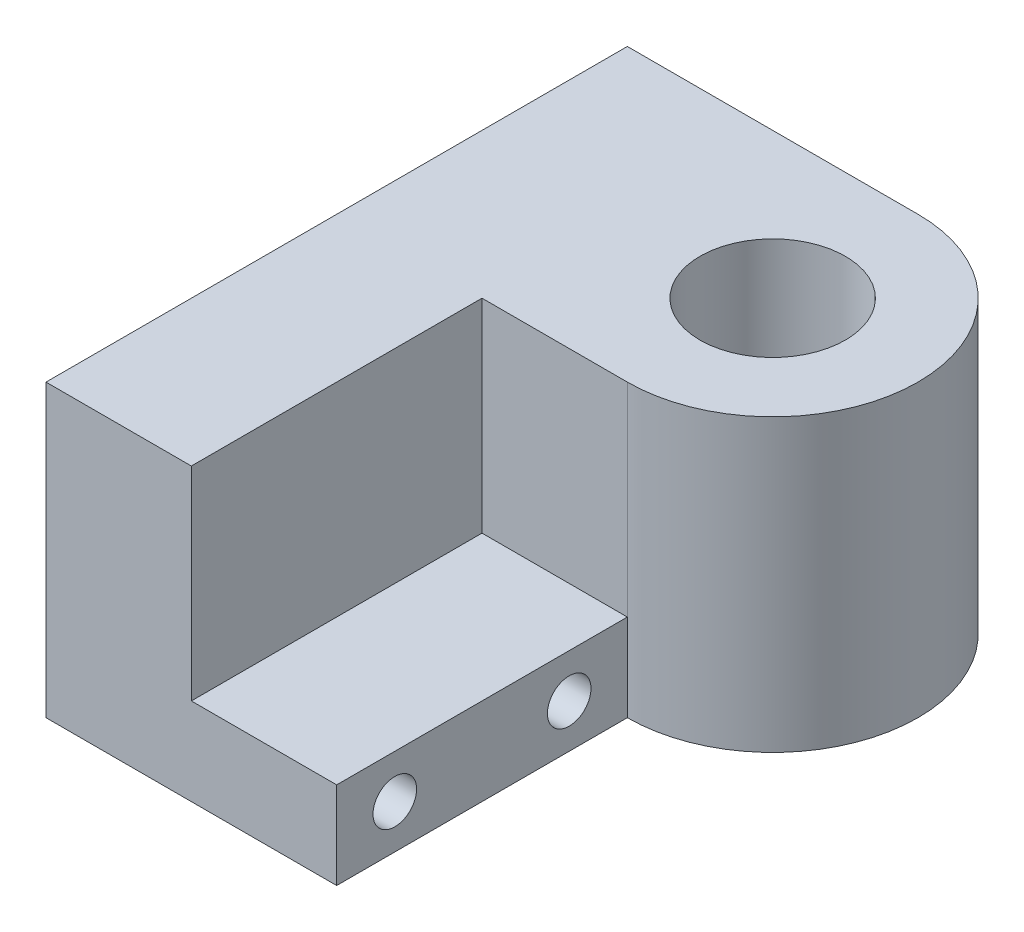
SolidWorks part; units mm, degrees
material "AISI 304"
ref_plane "Alzado" through (0, 0, 0) normal (0, 0, 1) x (1, 0, 0)
ref_plane "Planta" through (0, 0, 0) normal (0, 1, 0) x (1, 0, 0)
ref_plane "Vista lateral" through (0, 0, 0) normal (1, 0, 0) x (0, 0, -1)
sketch "Croquis3" plane through (0, 0, 0) normal (0, 1, 0) x (1, 0, 0)
  line L0 (0, 50) -> (-100, 50)
  line L1 (-100, 50) -> (-100, -150)
  line L2 (-100, -150) -> (-50, -150)
  line L3 (-50, -150) -> (-50, -50)
  line L4 (-50, -150) -> (0, -150)
  line L5 (0, -150) -> (0, -50)
  line L6 (0, -50) -> (-50, -50)
  circle A0 centre (0, 0) radius 25
  arc A1 (0, -50) -> (0, 50) centre (0, 0) ccw
  dimension "D1" = 100
  dimension "D3" = 200
  dimension "D4" = 100
  dimension "D2" = 50
  dimension "D5" = 100
extrude "Saliente-Extruir2" add sketch "Croquis3" along normal blind 100 contours L6 A1 L0 L1 L2 L3 A0 region at (-46.6688, 0, 29.4751)
extrude "Saliente-Extruir3" add sketch "Croquis3<3>" along normal blind 30 contours L5 L6 L3 L4 region at (-25, 0, 100)
sketch "Croquis3<3>" plane through (0, 0, 0) normal (0, 1, 0) x (1, 0, 0) same geometry as "Croquis3"
sketch "Croquis4" plane through (0, 0, 0) normal (1, 0, 0) x (0, 0, -1)
  line L0 (-150, 15) -> (-50, 15) construction
  line L1 (-150, 30) -> (-150, 0) construction
  line L2 (-50, 30) -> (-50, 0) construction
  line L3 (-100, 30) -> (-100, 0) construction
  line L4 (-150, 30) -> (-50, 30) construction
  line L5 (-150, 0) -> (-50, 0) construction
  circle A0 centre (-130, 15) radius 7.5
  circle A1 centre (-70, 15) radius 7.5
  dimension "D1" = 130
  dimension "D2" = 15
extrude "Cortar-Extruir1" cut sketch "Croquis4" against normal through all
